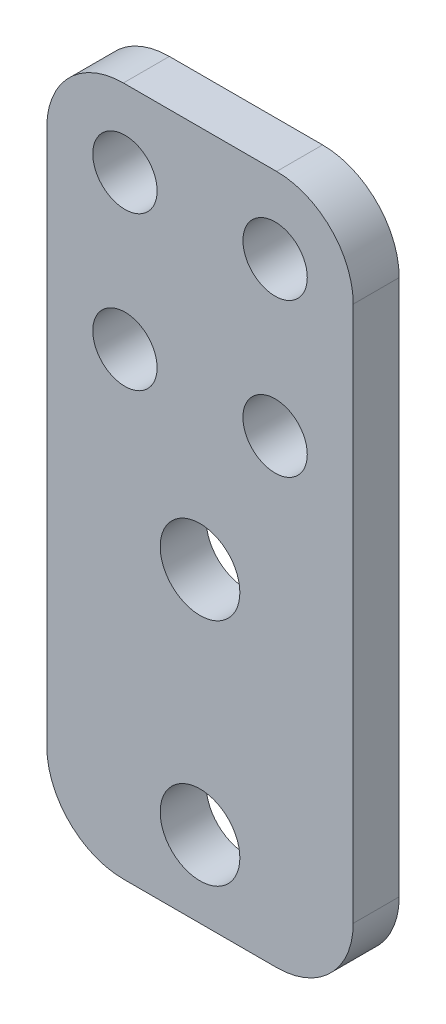
SolidWorks part; units mm, degrees
ref_plane "正面" through (0, 0, 0) normal (0, 0, 1) x (1, 0, 0)
ref_plane "平面" through (0, 0, 0) normal (0, 1, 0) x (1, 0, 0)
ref_plane "右側面" through (0, 0, 0) normal (1, 0, 0) x (0, 0, -1)
sketch "ｽｹｯﾁ2" plane through (0, 0, 0) normal (0, 0, 1) x (1, 0, 0)
  line L0 (0, 0) -> (0, -30) construction
  line L1 (-4.9, -5) -> (4.9, -5) construction
  line L2 (-4.9, -5) -> (-4.9, 5) construction
  line L3 (-4.9, 5) -> (4.9, 5) construction
  line L4 (4.9, -5) -> (4.9, 5) construction
  line L5 (-4.9, -5) -> (4.9, 5) construction
  line L6 (-4.9, 5) -> (4.9, -5) construction
  line L8 (-10, -35) -> (10, -35)
  line L9 (-10, -35) -> (-10, 10)
  line L10 (-10, 10) -> (10, 10)
  line L11 (10, -35) -> (10, 10)
  line L12 (-10, -35) -> (10, 10) construction
  line L13 (-10, 10) -> (10, -35) construction
  circle A0 centre (-4.9, 5) radius 2.1
  circle A1 centre (-4.9, -5) radius 2.1
  circle A2 centre (4.9, -5) radius 2.1
  circle A3 centre (4.9, 5) radius 2.1
  circle A4 centre (0, -30) radius 2.6
  circle A5 centre (0, -15) radius 2.6
  point P0 (0, 0)
  point P13 (0, -12.5)
  dimension "D1" = 4.2
  dimension "D4" = 5.2
  dimension "D5" = 10
  dimension "D9" = 15
  dimension "D2" = 10
  dimension "D3" = 9.8
  dimension "D6" = 20
  dimension "D7" = 5
  dimension "D8" = 5
extrude "ﾎﾞｽ - 押し出し1" add sketch "ｽｹｯﾁ2" along normal blind 3
fillet "ﾌｨﾚｯﾄ1" radius 5 4 edges at (-10, -35, 1.5) (10, -35, 1.5) (-10, 10, 1.5) (10, 10, 1.5)
